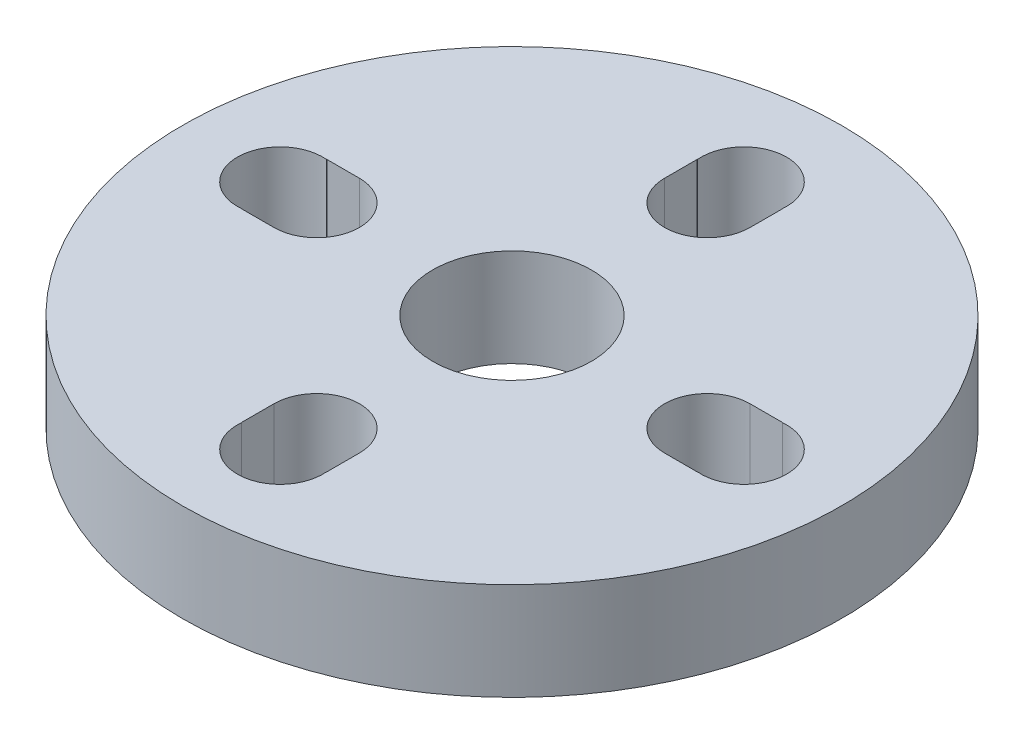
SolidWorks part; units mm, degrees
ref_plane "Front Plane" through (0, 0, 0) normal (0, 0, 1) x (1, 0, 0)
ref_plane "Top Plane" through (0, 0, 0) normal (0, 1, 0) x (1, 0, 0)
ref_plane "Right Plane" through (0, 0, 0) normal (1, 0, 0) x (0, 0, -1)
sketch "Sketch1" plane through (0, 0, 0) normal (0, 1, 0) x (1, 0, 0)
  circle A0 centre (0, 0) radius 13.5
  dimension "D1" = 27
extrude "Boss-Extrude1" add sketch "Sketch1" along normal blind 4
sketch "Sketch2" plane through (0, 4, 0) normal (0, 1, 0) x (1, 0, 0)
  line L0 (-13.5, 0) -> (13.5, 0) construction
  line L1 (0, 13.5) -> (0, -13.5) construction
  line L2 (-9.5, 1.75) -> (-8, 1.75)
  line L3 (-9.5, -1.75) -> (-8, -1.75)
  line L4 (0, 0) -> (9.5459, 9.5459) construction
  line L5 (9.5, -1.75) -> (8, -1.75)
  line L6 (9.5, 1.75) -> (8, 1.75)
  line L7 (-1.75, -9.5) -> (-1.75, -8)
  line L8 (1.75, -9.5) -> (1.75, -8)
  line L9 (1.75, 9.5) -> (1.75, 8)
  line L10 (-1.75, 9.5) -> (-1.75, 8)
  circle A0 centre (0, 0) radius 8
  circle A1 centre (0, 0) radius 9.5
  circle A2 centre (0, 0) radius 13.5 construction
  circle A3 centre (-9.5, 0) radius 1.75
  circle A4 centre (-8, 0) radius 1.75
  circle A5 centre (8, 0) radius 1.75
  circle A6 centre (9.5, 0) radius 1.75
  circle A7 centre (0, -8) radius 1.75
  circle A8 centre (0, -9.5) radius 1.75
  circle A9 centre (0, 8) radius 1.75
  circle A10 centre (0, 9.5) radius 1.75
  circle A11 centre (0, 0) radius 3.25
  dimension "D1" = 19
  dimension "D2" = 16
  dimension "D3" = 3.5
  dimension "D5" = 6.5
  dimension "D4" = 45
extrude "Cut-Extrude1" cut sketch "Sketch2" against normal up to next contours A4 A3 A1 L3 | A4 L2 A1 A3 | A10 A9 L9 A1 | A10 A1 L10 A9 | A1 A6 A5 L5 | A5 A6 A1 L6 | A7 A8 A1 L8 | A1 A8 A7 L7 | A3 | A4 | A9 | A10 | A5 | A6 | A8 | A7 | A11 region at (-8.7469, 4, -1.6996) region at (-1.6996, 4, -8.7469) region at (-8.7469, 4, 1.6996) region at (-1.6996, 4, 8.7469) region at (1.6996, 4, -8.7469) region at (8.7469, 4, -1.6996) region at (1.6996, 4, 8.7469) region at (8.7469, 4, 1.6996)
sketch "Sketch3" plane through (0, 4, 0) normal (0, 1, 0) x (1, 0, 0)
  line L1 (13.5, 13.5) -> (-13.5, 13.5)
  line L2 (13.5, 13.5) -> (13.5, -13.5)
  line L3 (13.5, -13.5) -> (-13.5, -13.5)
  line L4 (-13.5, 13.5) -> (-13.5, -13.5)
  line L5 (13.5, 13.5) -> (-13.5, -13.5) construction
  line L6 (13.5, -13.5) -> (-13.5, 13.5) construction
  circle A0 centre (0, 0) radius 13.5 construction
  point P0 (0, 0)
